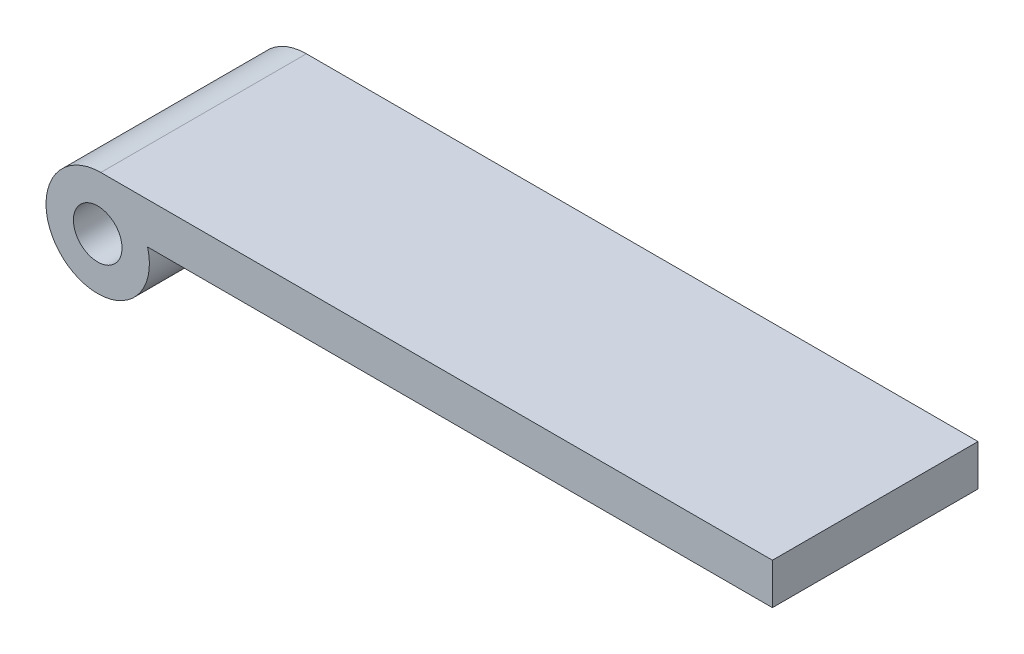
SolidWorks part; units mm, degrees
ref_plane "Front Plane" through (0, 0, 0) normal (0, 0, 1) x (1, 0, 0)
ref_plane "Top Plane" through (0, 0, 0) normal (0, 1, 0) x (1, 0, 0)
ref_plane "Right Plane" through (0, 0, 0) normal (1, 0, 0) x (0, 0, -1)
sketch "Sketch1" plane through (0, 0, 0) normal (0, 1, 0) x (1, 0, 0)
  line L1 (-16.8275, 4.7625) -> (16.8275, 4.7625)
  line L2 (-16.8275, 4.7625) -> (-16.8275, -4.7625)
  line L3 (-16.8275, -4.7625) -> (16.8275, -4.7625)
  line L4 (16.8275, 4.7625) -> (16.8275, -4.7625)
  line L5 (-16.8275, 4.7625) -> (16.8275, -4.7625) construction
  line L6 (-16.8275, -4.7625) -> (16.8275, 4.7625) construction
  point P0 (0, 0)
  dimension "D1" = 33.655
  dimension "D2" = 9.525
extrude "Boss-Extrude1" add sketch "Sketch1" along normal blind 5.08
sketch "Sketch4" plane through (0, 0, 4.7625) normal (0, 0, 1) x (1, 0, 0)
  line L0 (-14.4325, 2.54) -> (-14.4325, 0) construction
  line L3 (-16.8275, 0) -> (16.8275, 0) construction
  line L4 (-14.4325, 2.54) -> (-14.4325, 5.08) construction
  line L6 (-16.8275, 5.08) -> (16.8275, 5.08) construction
  line L8 (-16.8275, 5.08) -> (-16.8275, 0) construction
  circle A2 centre (-14.4325, 2.54) radius 1.125
  dimension "D1" = 2.25
  dimension "D2" = 1.27
extrude "Cut-Extrude2" cut sketch "Sketch4" against normal through all
fillet "Fillet1" radius 2.54 2 edges at (-16.8275, 0, 0) (-16.8275, 5.08, 0)
sketch "Sketch5" plane through (0, 0, 4.7625) normal (0, 0, 1) x (1, 0, 0)
  line L0 (16.8275, 5.08) -> (16.8275, 0) construction
  line L2 (16.8275, 3.175) -> (16.8275, 0)
  line L3 (16.8275, 0) -> (-14.2875, 0)
  line L5 (16.8275, 3.175) -> (-12.1232, 3.175)
  circle A0 centre (-14.4325, 2.54) radius 2.395
  arc A1 (-14.2875, 0) -> (-16.8275, 2.54) centre (-14.2875, 2.54) cw
  arc A2 (-16.8275, 2.54) -> (-14.2875, 0) centre (-14.2875, 2.54) ccw construction
  arc A3 (-14.2875, 5.08) -> (-16.8275, 2.54) centre (-14.2875, 2.54) ccw construction
  dimension "D1" = 4.79
  dimension "D2" = 1.905
extrude "Cut-Extrude3" cut sketch "Sketch5" along direction (0, 0, -1) on the side against the normal through all
